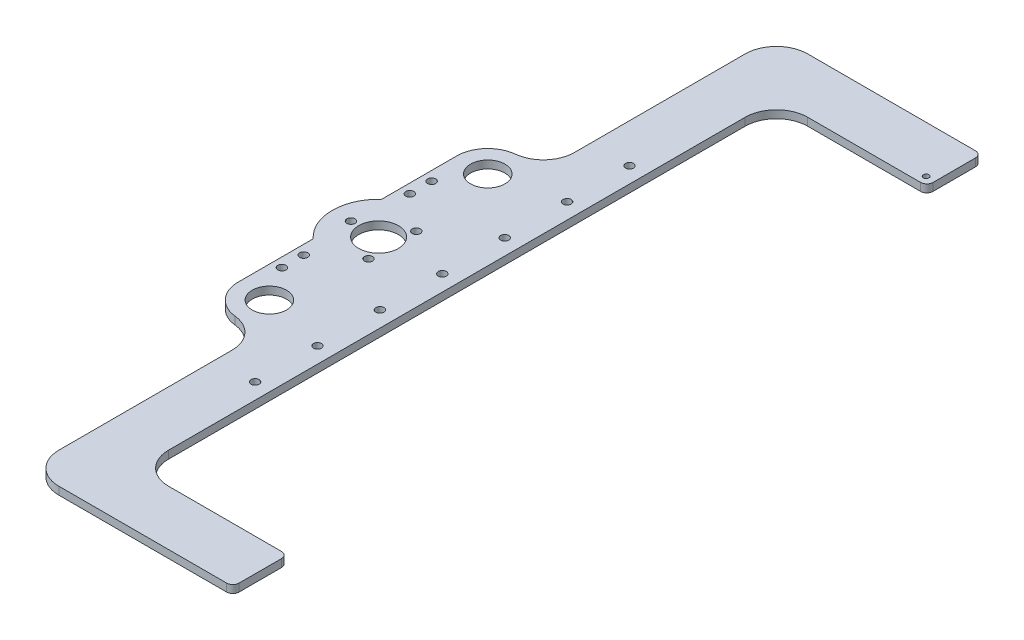
SolidWorks part; units mm, degrees
ref_plane "Front Plane" through (0, 0, 0) normal (0, 0, 1) x (1, 0, 0)
ref_plane "Top Plane" through (0, 0, 0) normal (0, 1, 0) x (1, 0, 0)
ref_plane "Right Plane" through (0, 0, 0) normal (1, 0, 0) x (0, 0, -1)
sketch "Sketch1" plane through (0, 0, 0) normal (0, 1, 0) x (1, 0, 0)
  line L0 (-67.9713, -52.7283) -> (-67.9713, -82.5864)
  line L1 (-45.2284, -108.5097) -> (-45.2284, -114.9973)
  line L3 (-22.9035, -128.2046) -> (-22.9035, 49.5954)
  line L5 (-45.2284, 37.4027) -> (-45.2284, 30.9152)
  line L6 (-67.9713, 4.9919) -> (-67.9713, -24.8662)
  line L7 (-45.2284, 49.5954) -> (-45.2284, 37.4027)
  line L13 (-22.9035, 49.5954) -> (-22.9035, 78.0705)
  line L14 (-22.9035, 113.0954) -> (-32.5284, 113.0954)
  line L15 (-45.2284, 49.5954) -> (-45.2284, 100.3954)
  line L16 (-45.2284, -114.9973) -> (-45.2284, -128.2046)
  line L19 (-45.2284, -128.2046) -> (-45.2284, -179.0046)
  line L20 (-32.5284, -191.7046) -> (-22.9035, -191.7046)
  line L21 (-22.9035, -128.2046) -> (-22.9035, -156.6798)
  line L22 (-22.9035, 113.0954) -> (38.3105, 113.0954)
  line L24 (-10.2035, 90.7705) -> (38.3105, 90.7705)
  line L25 (38.3105, 113.0954) -> (38.3105, 90.7705)
  line L26 (-22.9035, -191.7046) -> (38.3105, -191.7046)
  line L28 (-10.2035, -169.3798) -> (38.3105, -169.3798)
  line L29 (38.3105, -191.7046) -> (38.3105, -169.3798)
  arc A0 (-67.9713, -82.5864) -> (-56.6084, -95.8785) centre (-55.2885, -83.2473) ccw
  arc A1 (-45.2284, -108.5097) -> (-56.6084, -95.8785) centre (-57.9284, -108.5097) ccw
  arc A4 (-56.6084, 18.284) -> (-45.2284, 30.9152) centre (-57.9284, 30.9152) ccw
  arc A5 (-56.6084, 18.284) -> (-67.9713, 4.9919) centre (-55.2885, 5.6527) ccw
  arc A6 (-67.9713, -24.8662) -> (-67.9713, -52.7283) centre (-55.2885, -38.7973) ccw
  arc A22 (-45.2284, 100.3954) -> (-32.5284, 113.0954) centre (-32.5284, 100.3954) cw
  arc A23 (-45.2284, -179.0046) -> (-32.5284, -191.7046) centre (-32.5284, -179.0046) ccw
  arc A24 (-22.9035, 78.0705) -> (-10.2035, 90.7705) centre (-10.2035, 78.0705) cw
  arc A25 (-22.9035, -156.6798) -> (-10.2035, -169.3798) centre (-10.2035, -156.6798) ccw
  circle A26 centre (34.7545, 94.0725) radius 1.143
  circle A30 centre (-55.2885, -83.2473) radius 6.985 construction
  circle A31 centre (-64.1613, -69.2773) radius 1.65 construction
  circle A32 centre (-64.1613, -60.3873) radius 1.65 construction
  circle A33 centre (-55.2885, -38.7973) radius 8.0645 construction
  circle A34 centre (-49.6688, -29.0636) radius 1.65 construction
  circle A35 centre (-49.6688, -48.531) radius 1.65 construction
  circle A36 centre (-66.528, -38.7973) radius 1.65 construction
  circle A37 centre (-64.1613, -17.2073) radius 1.65 construction
  circle A38 centre (-64.1613, -8.3173) radius 1.65 construction
  circle A39 centre (-55.2885, 5.6527) radius 6.985 construction
  circle A40 centre (-55.2885, -83.2473) radius 6.985
  circle A41 centre (-64.1613, -69.2773) radius 1.65
  circle A42 centre (-64.1613, -60.3873) radius 1.65
  circle A43 centre (-55.2885, -38.7973) radius 8.0645
  circle A44 centre (-49.6688, -29.0636) radius 1.65
  circle A45 centre (-49.6688, -48.531) radius 1.65
  circle A46 centre (-66.528, -38.7973) radius 1.65
  circle A47 centre (-64.1613, -17.2073) radius 1.65
  circle A48 centre (-64.1613, -8.3173) radius 1.65
  circle A49 centre (-55.2885, 5.6527) radius 6.985
  circle A50 centre (-29.342, 37.4027) radius 1.65 construction
  circle A51 centre (-29.342, 12.0027) radius 1.65 construction
  circle A52 centre (-29.342, -13.3973) radius 1.65 construction
  circle A53 centre (-29.342, -38.7973) radius 1.65 construction
  circle A54 centre (-29.342, -64.1973) radius 1.65 construction
  circle A55 centre (-29.342, -89.5973) radius 1.65 construction
  circle A56 centre (-29.342, -114.9973) radius 1.65 construction
  circle A57 centre (-29.342, 37.4027) radius 1.65
  circle A58 centre (-29.342, 12.0027) radius 1.65
  circle A59 centre (-29.342, -13.3973) radius 1.65
  circle A60 centre (-29.342, -38.7973) radius 1.65
  circle A61 centre (-29.342, -64.1973) radius 1.65
  circle A62 centre (-29.342, -89.5973) radius 1.65
  circle A63 centre (-29.342, -114.9973) radius 1.65
  point P58 (-45.2284, 113.0954)
  dimension "D5" = 2.286
  dimension "D6" = 3.302
  dimension "D7" = 3.556
  dimension "D37" = 63.5
  dimension "D44" = 12.7
  dimension "D45" = 12.7
  dimension "D46" = 12.7
  dimension "D47" = 12.7
  dimension "D1" = 177.8
  dimension "D2" = 32.385
  dimension "D30" = 304.8
  dimension "D31" = 22.3249
  dimension "D36" = 22.3249
  dimension "D38" = 22.3249
  dimension "D39" = 22.3249
  dimension "D40" = 61.214
  dimension "D41" = 61.214
extrude "Boss-Extrude1" add sketch "Sketch1" along normal blind 3.175
fillet "Fillet1" radius 2.54 4 edges at (38.3105, 1.5875, -113.0954) (38.3105, 1.5875, -90.7705) (38.3105, 1.5875, 169.3798) (38.3105, 1.5875, 191.7046)
